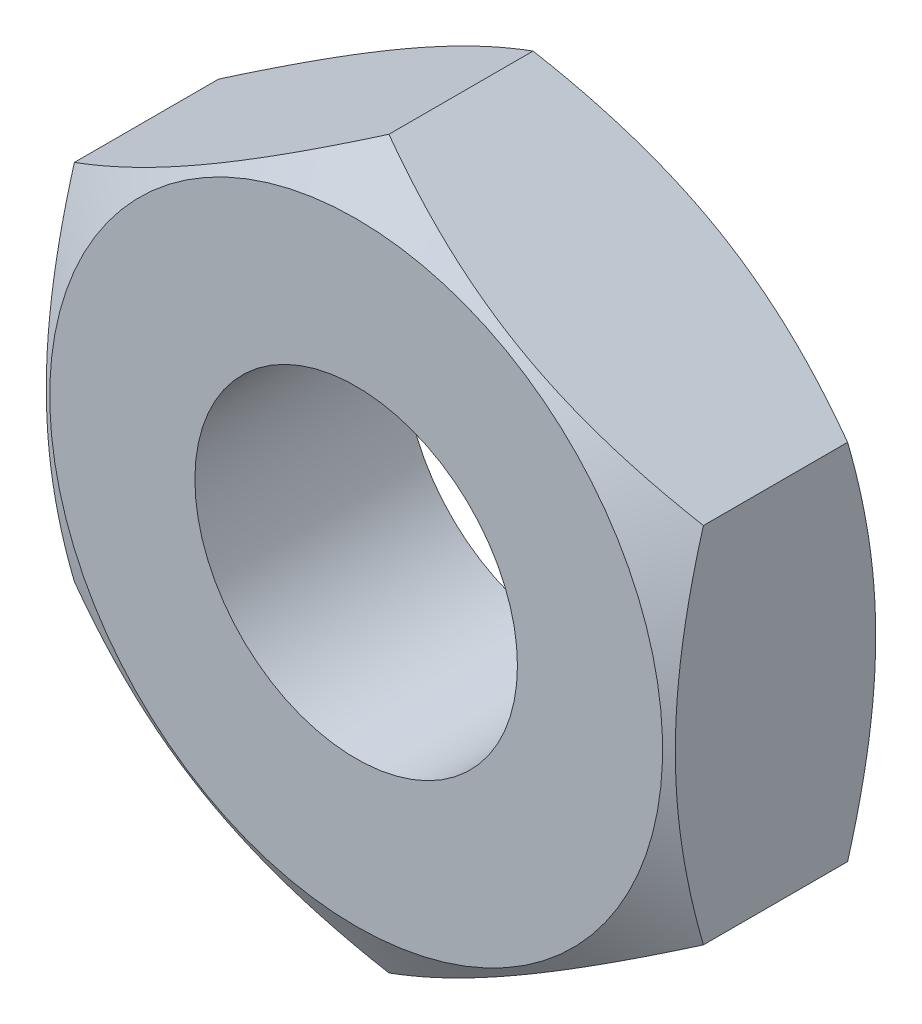
SolidWorks part; units mm, degrees
ref_plane "Спереди" through (0, 0, 0) normal (0, 0, 1) x (1, 0, 0)
ref_plane "Сверху" through (0, 0, 0) normal (0, 1, 0) x (1, 0, 0)
ref_plane "Справа" through (0, 0, 0) normal (1, 0, 0) x (0, 0, -1)
sketch "Sketch1" plane through (0, 0, 0) normal (0, 0, 1) x (1, 0, 0)
  line L7 (0, 2.2517) -> (-1.95, 1.1258)
  line L8 (-1.95, 1.1258) -> (-1.95, -1.1258)
  line L9 (-1.95, -1.1258) -> (0, -2.2517)
  line L10 (0, -2.2517) -> (1.95, -1.1258)
  line L11 (1.95, -1.1258) -> (1.95, 1.1258)
  line L12 (1.95, 1.1258) -> (0, 2.2517)
  circle A0 centre (0, 0) radius 1
  circle A1 centre (0, 0) radius 1.95 construction
extrude "Extrude1" add sketch "Sketch1" along normal blind 1.3
sketch "Sketch2" plane through (0, 0, 0) normal (1, 0, 0) x (0, 0, -1)
  line L0 (0, 1.9) -> (-0.7615, 3.219)
  line L1 (0, 1.9) -> (0, 5.1947)
  line L2 (-1.3, 0) -> (0, 0)
  line L3 (-1.3, -1.1258) -> (-1.3, 1.1258) construction
  line L4 (-0.65, 0) -> (-0.65, -3.3526) construction
  line L5 (-1.3, 1.9) -> (-1.3, 5.1947)
  line L6 (-1.3, 1.9) -> (-0.5385, 3.219)
  line L7 (-3.1638, 2.6533) -> (0.8049, 2.6533)
  circle A0 centre (0, 0) radius 1.9
  circle A1 centre (-1.3, 0) radius 1.9
revolve "Cut-Revolve1" cut sketch "Sketch2" angle 360 about L2 region at (0, 2.4022, 0.145) region at (0, 2.4022, 1.155)
